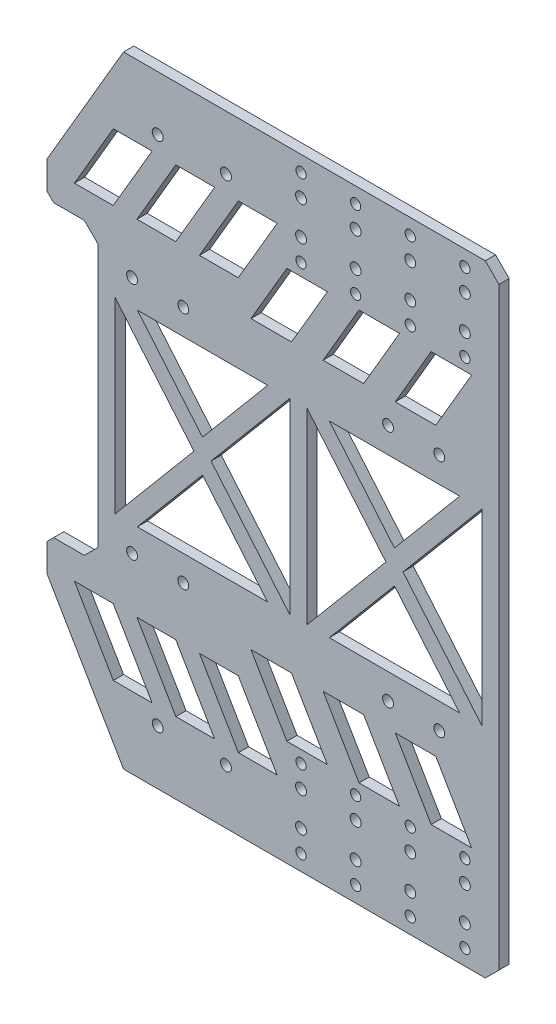
SolidWorks part; units mm, degrees
material "Thornel Mat VMA"
ref_plane "前视基准面" through (0, 0, 0) normal (0, 0, 1) x (1, 0, 0)
ref_plane "上视基准面" through (0, 0, 0) normal (0, 1, 0) x (1, 0, 0)
ref_plane "右视基准面" through (0, 0, 0) normal (1, 0, 0) x (0, 0, -1)
sketch "草图1" plane through (0, 0, 0) normal (0, 0, 1) x (1, 0, 0)
  line L1 (-99, 91) -> (99, 91)
  line L2 (-99, 91) -> (-99, -91)
  line L3 (-99, -91) -> (99, -91)
  line L4 (99, 91) -> (99, -91)
  line L5 (-99, 91) -> (99, -91) construction
  line L6 (-99, -91) -> (99, 91) construction
  point P0 (0, 0)
  dimension "D1" = 182
  dimension "D2" = 198
extrude "凸台-拉伸1" add sketch "草图1" along normal blind 3
sketch "草图3" plane through (0, 0, 0) normal (0, 0, -1) x (-1, 0, 0)
  line L0 (-39, -91) -> (-39, -80) construction
  line L1 (99, -91) -> (-99, -91) construction
  line L2 (-99, -91) -> (-99, 91) construction
  line L3 (-39, -80) -> (-39, -70) construction
  line L4 (87, -91) -> (87, -80) construction
  line L5 (99, 91) -> (99, -91) construction
  line L6 (87, -80) -> (87, -70) construction
  line L7 (0, 0) -> (-55, 0) construction
  line L8 (87, 80) -> (87, 70) construction
  line L9 (87, 91) -> (87, 80) construction
  line L10 (-39, 80) -> (-39, 70) construction
  line L11 (-39, 91) -> (-39, 80) construction
  circle A0 centre (-39, -80) radius 1.6
  circle A1 centre (-39, -70) radius 1.6
  circle A2 centre (-23, -80) radius 1.6
  circle A3 centre (-23, -70) radius 1.6
  circle A4 centre (-7, -80) radius 1.6
  circle A5 centre (-7, -70) radius 1.6
  circle A6 centre (9, -80) radius 1.6
  circle A7 centre (9, -70) radius 1.6
  circle A8 centre (87, -80) radius 1.6
  circle A9 centre (87, -70) radius 1.6
  circle A10 centre (71, -80) radius 1.6
  circle A11 centre (71, -70) radius 1.6
  circle A12 centre (55, -80) radius 1.6
  circle A13 centre (55, -70) radius 1.6
  circle A14 centre (39, -80) radius 1.6
  circle A15 centre (39, -70) radius 1.6
  circle A16 centre (39, 70) radius 1.6
  circle A17 centre (39, 80) radius 1.6
  circle A18 centre (55, 70) radius 1.6
  circle A19 centre (55, 80) radius 1.6
  circle A20 centre (71, 70) radius 1.6
  circle A21 centre (71, 80) radius 1.6
  circle A22 centre (87, 70) radius 1.6
  circle A23 centre (87, 80) radius 1.6
  circle A24 centre (9, 70) radius 1.6
  circle A25 centre (9, 80) radius 1.6
  circle A26 centre (-7, 70) radius 1.6
  circle A27 centre (-7, 80) radius 1.6
  circle A28 centre (-23, 70) radius 1.6
  circle A29 centre (-23, 80) radius 1.6
  circle A30 centre (-39, 70) radius 1.6
  circle A31 centre (-39, 80) radius 1.6
  dimension "D3" = 3.2
  dimension "D5" = 3.2
  dimension "D9" = 3.2
  dimension "D11" = 3.2
  dimension "D1" = 11
  dimension "D2" = 60
  dimension "D4" = 10
  dimension "D7" = 11
  dimension "D8" = 12
  dimension "D10" = 10
  dimension "D6" = 4
  dimension "D12" = 4
extrude "切除-拉伸2" cut sketch "草图3" against normal up to next (3 mm away)
sketch "草图4" plane through (0, 0, 0) normal (0, 0, -1) x (-1, 0, 0)
  line L0 (-99, -91) -> (-51, -91)
  line L1 (99, -91) -> (-99, -91) construction
  line L2 (-51, -91) -> (-51, 91)
  line L3 (-99, 91) -> (99, 91) construction
  line L4 (-51, 91) -> (-99, 91)
  line L5 (-99, 91) -> (-99, -91)
  dimension "D1" = 48
extrude "切除-拉伸3" cut sketch "草图4" against normal up to next
sketch "草图5" plane through (0, 0, 3) normal (0, 0, 1) x (1, 0, 0)
  line L0 (-99, 0) -> (-139, 0) construction
  line L3 (-99, 91) -> (-99, -91) construction
  line L4 (-99, -91) -> (51, -91) construction
  line L5 (-98.9551, 56) -> (-139.0449, 56)
  line L6 (-98.9551, 56) -> (-98.9551, -56)
  line L7 (-98.9551, -56) -> (-139.0449, -56)
  line L8 (-139.0449, 56) -> (-139.0449, -56)
  line L9 (-98.9551, 56) -> (-139.0449, -56) construction
  line L10 (-98.9551, -56) -> (-139.0449, 56) construction
  point P5 (71, 0)
  point P6 (-119, 0)
  dimension "D1" = 40
  dimension "D2" = 35
extrude "凸台-拉伸2" add sketch "草图5" against normal up to surface (3 mm away) up to face at (40.6, 80, 0)
sketch "草图6" plane through (0, 0, 3) normal (0, 0, 1) x (1, 0, 0)
  line L0 (-99, -91) -> (51, -91) construction
  line L1 (51, -91) -> (51, 91) construction
  line L2 (51, 0) -> (-28.0996, 0) construction
  circle A0 centre (13, -37) radius 2.75
  circle A1 centre (13, 37) radius 2.75
  circle A2 centre (-57, 37) radius 2.75
  circle A3 centre (-57, -37) radius 2.75
  circle A4 centre (-127, 37) radius 2.75
  circle A5 centre (-127, -37) radius 2.75
  dimension "D3" = 5.5
  dimension "D1" = 54
  dimension "D2" = 38
  dimension "D4" = 3
extrude "切除-拉伸4" cut sketch "草图6" against normal up to next
sketch "草图7" plane through (0, 0, 3) normal (0, 0, 1) x (1, 0, 0)
  line L0 (51, 0) -> (-44.0224, 0) construction
  line L1 (51, -91) -> (51, 91) construction
  line L3 (-44.0224, 0) -> (-44.0224, 48.7453) construction
  line L4 (-29.0112, -15) -> (-19.0112, -25)
  line L5 (-19.0112, -25) -> (25.9888, -25)
  line L6 (-29.0112, -15) -> (-29.0112, 15)
  line L7 (-19.0112, 25) -> (25.9888, 25)
  line L8 (35.9888, -15) -> (35.9888, 15)
  line L9 (-29.0112, -25) -> (35.9888, 25) construction
  line L10 (-29.0112, 25) -> (35.9888, -25) construction
  line L11 (-29.0112, 15) -> (-19.0112, 25)
  line L12 (25.9888, -25) -> (35.9888, -15)
  line L13 (35.9888, 15) -> (25.9888, 25)
  line L14 (-114.0337, -25) -> (-124.0337, -15)
  line L15 (-124.0337, -15) -> (-124.0337, 15)
  line L16 (-124.0337, 15) -> (-114.0337, 25)
  line L17 (-69.0337, 25) -> (-114.0337, 25)
  line L18 (-59.0337, 15) -> (-69.0337, 25)
  line L19 (-59.0337, -15) -> (-59.0337, 15)
  line L20 (-59.0337, -15) -> (-69.0337, -25)
  line L21 (-69.0337, -25) -> (-114.0337, -25)
  point P1 (3.4888, 0)
  dimension "D1" = 50
  dimension "D2" = 65
extrude "切除-拉伸5" cut sketch "草图7" against normal up to next
sketch "草图8" plane through (0, 0, 3) normal (0, 0, 1) x (1, 0, 0)
  line L0 (-99, -56) -> (-139.0449, -56)
  line L1 (-139.0449, -56) -> (-99, -91)
  line L2 (-99, -91) -> (-99, -56)
  line L3 (-139.0449, 56) -> (-99, 91)
  line L4 (-99, 91) -> (-99, 56)
  line L5 (-99, 56) -> (-139.0449, 56)
extrude "凸台-拉伸3" add sketch "草图8" against normal up to surface (3 mm away) up to face at (-91.5337, 0, 0)
sketch "草图10" plane through (0, 0, 3) normal (0, 0, 1) x (1, 0, 0)
  line L0 (-139.0449, 0) -> (51, 0) construction
  line L1 (-139.0449, 56) -> (-139.0449, -56) construction
  line L2 (51, -91) -> (51, 91) construction
  line L3 (-127, -42) -> (-127, -55.7313)
  line L4 (-127, -55.7313) -> (-115.2512, -66)
  line L5 (-115.2512, -66) -> (41, -66)
  line L6 (41, -66) -> (41, 66)
  line L7 (-127, -32) -> (-127, 32)
  line L8 (-99, -91) -> (51, -91) construction
  line L10 (-115.2512, 66) -> (41, 66)
  line L11 (-127, 55.7313) -> (-115.2512, 66)
  line L12 (-127, 42) -> (-127, 55.7313)
  circle A0 centre (-57, 37) radius 5
  circle A1 centre (-127, 37) radius 5
  circle A2 centre (13, 37) radius 5
  arc A3 (-127, -42) -> (-127, -32) centre (-127, -37) ccw
  circle A4 centre (-57, -37) radius 5
  circle A5 centre (13, -37) radius 5
  point P33 (41, 0)
  point P37 (-127, 0)
  dimension "D1" = 10
  dimension "D2" = 10
  dimension "D3" = 10
  dimension "D4" = 10
  dimension "D5" = 10
  dimension "D6" = 10
  dimension "D7" = 10
  dimension "D8" = 25
extrude "切除-拉伸6" cut sketch "草图10" against normal blind 10 contours L7 L0 L6 L10 L11 L12 A1 A0 A2 | L0 L7 A3 L3 L4 L5 L6 A5 A4 region at (-42.5617, 32.7628, 3) region at (-42.5617, -32.7628, 3)
sketch "草图11" plane through (0, 0, 3) normal (0, 0, 1) x (1, 0, 0)
  line L0 (-124.25, -37) -> (-59.75, -37)
  line L1 (-57, -39.75) -> (-57, -67.3473)
  line L2 (-54.25, -37) -> (10.25, -37)
  line L3 (13, -39.75) -> (13, -67.3473)
  line L4 (-124.25, 37) -> (-59.75, 37)
  line L5 (15.75, -37) -> (43.7296, -37)
  line L6 (-54.25, 37) -> (10.25, 37)
  line L7 (15.75, 37) -> (41.6506, 37)
  circle A0 centre (-127, -37) radius 2.75 construction
  circle A1 centre (-57, -37) radius 2.75 construction
  circle A2 centre (13, -37) radius 2.75 construction
  circle A3 centre (-127, 37) radius 2.75 construction
  circle A4 centre (-57, 37) radius 2.75 construction
  circle A5 centre (13, 37) radius 2.75 construction
extrude "拉伸-薄壁1" add sketch "草图11" against normal up to surface (3 mm away) thin up to face at (37.4, -80, 0) thin type mid plane wall 5
sketch "草图12" plane through (0, 0, 3) normal (0, 0, 1) x (1, 0, 0)
  line L0 (-57, 39.75) -> (-57, 67.3397)
  line L1 (13, 39.75) -> (13, 68.5019)
  line L2 (13, -34.25) -> (13, 34.25)
  line L3 (-57, -34.25) -> (-57, 34.25)
  circle A0 centre (-57, 37) radius 2.75 construction
  circle A1 centre (13, 37) radius 2.75 construction
  circle A2 centre (13, -37) radius 2.75 construction
  circle A3 centre (-57, -37) radius 2.75 construction
extrude "拉伸-薄壁2" add sketch "草图12" against normal up to surface (3 mm away) thin up to face at (-42.3336, 0, 0) thin type mid plane wall 5
sketch "草图13" plane through (0, 0, 3) normal (0, 0, 1) x (1, 0, 0)
  line L0 (-57, -37) -> (13, 37)
  line L2 (-57, 37) -> (-56.3876, 37.2464)
extrude "拉伸-薄壁3" add sketch "草图13" against normal up to surface (3 mm away) thin up to face at (-22, 0, 0) thin type mid plane wall 5
sketch "草图14" plane through (0, 0, 0) normal (0, 0, -1) x (-1, 0, 0)
  line L0 (57, 37) -> (-13, -37)
  line L1 (57.9332, 39.3193) -> (56.0668, 34.6807) construction
extrude "拉伸-薄壁4" add sketch "草图14" against normal up to surface (3 mm away) thin up to face at (-38.5889, 17.7076, 3) thin type mid plane wall 5
sketch "草图15" plane through (0, 0, 3) normal (0, 0, 1) x (1, 0, 0)
  line L0 (-55.1838, -38.718) -> (-58.8162, -35.282) construction
  line L2 (11.1838, -38.718) -> (14.8162, -35.282) construction
  line L3 (11.1838, 38.718) -> (14.8162, 35.282) construction
  circle A0 centre (-57, -37) radius 2.75
  circle A1 centre (-57, 37) radius 2.75
  circle A2 centre (13, 37) radius 2.75
  circle A3 centre (13, -37) radius 2.75
extrude "切除-拉伸7" cut sketch "草图15" against normal up to next
sketch "草图16" plane through (0, 0, 3) normal (0, 0, 1) x (1, 0, 0)
  line L0 (-57, -37) -> (-127, 37)
  line L1 (-57, 37) -> (-127, -37)
extrude "拉伸-薄壁5" add sketch "草图16" against normal up to surface (3 mm away) thin up to face at (-54.25, 37, 0) thin type mid plane wall 5
sketch "草图17" plane through (0, 0, 3) normal (0, 0, 1) x (1, 0, 0)
  line L0 (41, 34.5) -> (13, -37)
  line L1 (13, 37) -> (41, -34.5)
extrude "拉伸-薄壁6" add sketch "草图17" against normal up to surface (3 mm away) thin up to face at (-120.2229, 0, 0) thin type mid plane wall 5
sketch "草图18" plane through (0, 0, 0) normal (0, 0, -1) x (-1, 0, 0)
  line L0 (-10.6721, -36.0884) -> (-15.3279, -37.9116) construction
  line L1 (-15.3279, 37.9116) -> (-10.6721, 36.0884) construction
  line L2 (55.1838, 35.282) -> (58.8162, 38.718) construction
  line L3 (58.8162, -38.718) -> (55.1838, -35.282) construction
  line L4 (128.8162, -35.282) -> (125.1838, -38.718) construction
  line L5 (125.1838, 38.718) -> (128.8162, 35.282) construction
  circle A0 centre (-13, -37) radius 2.75
  circle A1 centre (-13, 37) radius 2.75
  circle A2 centre (57, 37) radius 2.75
  circle A3 centre (57, -37) radius 2.75
  circle A4 centre (127, -37) radius 2.75
  circle A5 centre (127, 37) radius 2.75
extrude "切除-拉伸8" cut sketch "草图18" against normal up to next
sketch "草图19" plane through (0, 0, 3) normal (0, 0, 1) x (1, 0, 0)
  line L0 (-57, 37) -> (10.5, 66)
  line L1 (13, 37) -> (-54.5, 66)
  line L2 (-127, 37) -> (-59.5, 66)
  line L3 (-57, 37) -> (-115.2512, 66)
  line L4 (13, 37) -> (41, 66)
  line L5 (15.5, 66) -> (41, 39.5)
extrude "拉伸-薄壁7" add sketch "草图19" against normal up to surface (3 mm away) thin up to face at (37.3915, 0, 0) thin type mid plane wall 5
sketch "草图20" plane through (0, 0, 0) normal (0, 0, -1) x (-1, 0, 0)
  line L0 (127.9869, 39.297) -> (126.0131, 34.703) construction
  circle A0 centre (-13, 37) radius 2.75
  circle A1 centre (57, 37) radius 2.75
  circle A2 centre (127, 37) radius 2.75
extrude "切除-拉伸9" cut sketch "草图20" against normal up to next
sketch "草图21" plane through (0, 0, 0) normal (0, 0, -1) x (-1, 0, 0)
  line L0 (-13, -37) -> (-41, -66)
  line L1 (-15.5, -66) -> (-41, -39.5)
  line L2 (-10.5, -66) -> (57, -37)
  line L3 (-13, -37) -> (54.5, -66)
  line L4 (57, -37) -> (115.2512, -66)
  line L5 (59.5, -66) -> (127, -37)
extrude "拉伸-薄壁8" add sketch "草图21" against normal up to surface (3 mm away) thin up to face at (-129.75, 37, 3) thin type mid plane wall 5
sketch "草图22" plane through (0, 0, 3) normal (0, 0, 1) x (1, 0, 0)
  line L0 (-126.0131, -34.703) -> (-127.9869, -39.297) construction
  circle A0 centre (-127, -37) radius 2.75
  circle A1 centre (-57, -37) radius 2.75
  circle A2 centre (13, -37) radius 2.75
extrude "切除-拉伸10" cut sketch "草图22" against normal up to next
sketch "草图23" plane through (0, 0, 3) normal (0, 0, 1) x (1, 0, 0)
  line L0 (-115.2512, 66) -> (-116.3654, 63.762)
  line L1 (-116.3654, 63.762) -> (-117.2869, 64.2208)
  line L2 (-127, 55.7313) -> (-115.2512, 66) construction
  line L3 (-117.2869, 64.2208) -> (-115.2512, 66)
  line L4 (-116.3654, -63.762) -> (-117.2869, -64.2208)
  line L5 (-127, -55.7313) -> (-115.2512, -66) construction
  line L6 (-117.2869, -64.2208) -> (-115.2512, -66)
  line L7 (-115.2512, -66) -> (-116.3654, -63.762)
extrude "凸台-拉伸4" add sketch "草图23" against normal up to surface (3 mm away) up to face at (-54.25, -37, 0)
sketch "草图24" plane through (0, 0, 0) normal (0, 0, -1) x (-1, 0, 0)
  line L0 (21.9465, 0) -> (-12.7555, 0)
extrude "拉伸-薄壁9" add sketch "草图24" against normal up to surface (3 mm away) thin up to face at (-118.1171, 51.302, 3) thin type mid plane wall 10
sketch "草图25" plane through (0, 0, 0) normal (0, 0, -1) x (-1, 0, 0)
  line L0 (20.7116, 5) -> (21.9465, 3.6945)
  line L1 (21.9465, 3.6945) -> (21.9465, 5)
  line L2 (21.9465, 5) -> (20.7116, 5)
  line L3 (20.7116, -5) -> (21.9465, -5)
  line L4 (21.9465, -5) -> (21.9465, -3.6945)
  line L5 (21.9465, -3.6945) -> (20.7116, -5)
extrude "切除-拉伸11" cut sketch "草图25" against normal up to next
sketch "草图26" plane through (0, 0, 0) normal (0, 0, -1) x (-1, 0, 0)
  line L0 (-13, -37) -> (-13, 37) construction
  line L1 (-13, 0) -> (7, 0) construction
  circle A0 centre (7, 0) radius 2.75
  dimension "D2" = 5.5
  dimension "D1" = 20
extrude "切除-拉伸12" cut sketch "草图26" against normal up to next
sketch "草图27" plane through (0, 0, 3) normal (0, 0, 1) x (1, 0, 0)
  line L0 (10.5, 5) -> (-2.3398, 17.1457)
  line L1 (-13.829, 5) -> (10.5, 30.7192) construction
  line L2 (-2.3398, 17.1457) -> (-13.829, 5)
  line L3 (-13.829, 5) -> (10.5, 5)
  line L4 (-13.829, -5) -> (10.5, -5)
  line L5 (10.5, -5) -> (-2.3398, -17.1457)
  line L6 (-13.829, -5) -> (10.5, -30.7192) construction
  line L7 (-2.3398, -17.1457) -> (-13.829, -5)
extrude "凸台-拉伸5" add sketch "草图27" against normal up to surface (3 mm away) up to face at (-9.75, 0, 0)
sketch "草图28" plane through (0, 0, 3) normal (0, 0, 1) x (1, 0, 0)
  line L1 (51, 91) -> (-199, 91)
  line L2 (51, 91) -> (51, -91)
  line L3 (51, -91) -> (-199, -91)
  line L4 (-199, 91) -> (-199, -91)
  circle A1 centre (-87, -70) radius 1.6
  circle A2 centre (-87, -70) radius 1.6
  circle A3 centre (-87, -80) radius 1.6
  circle A4 centre (-87, -80) radius 1.6
  circle A5 centre (-71, -70) radius 1.6
  circle A6 centre (-71, -70) radius 1.6
  circle A7 centre (-71, -80) radius 1.6
  circle A8 centre (-71, -80) radius 1.6
  circle A9 centre (-55, -70) radius 1.6
  circle A10 centre (-55, -70) radius 1.6
  circle A11 centre (-55, -80) radius 1.6
  circle A12 centre (-55, -80) radius 1.6
  circle A13 centre (-39, -70) radius 1.6
  circle A14 centre (-39, -70) radius 1.6
  circle A15 centre (-39, -80) radius 1.6
  circle A16 centre (-39, -80) radius 1.6
  circle A17 centre (-87, 80) radius 1.6
  circle A18 centre (-87, 80) radius 1.6
  circle A19 centre (-87, 70) radius 1.6
  circle A20 centre (-87, 70) radius 1.6
  circle A21 centre (-71, 80) radius 1.6
  circle A22 centre (-71, 80) radius 1.6
  circle A23 centre (-71, 70) radius 1.6
  circle A24 centre (-71, 70) radius 1.6
  circle A25 centre (-55, 80) radius 1.6
  circle A26 centre (-55, 80) radius 1.6
  circle A27 centre (-55, 70) radius 1.6
  circle A28 centre (-55, 70) radius 1.6
  circle A29 centre (-39, 80) radius 1.6
  circle A30 centre (-39, 80) radius 1.6
  circle A31 centre (-39, 70) radius 1.6
  circle A32 centre (-39, 70) radius 1.6
  dimension "D1" = 250
  dimension "D2" = 0
  dimension "D3" = 0
  dimension "D4" = 0
  dimension "D5" = 0
  dimension "D6" = 0
  dimension "D7" = 0
  dimension "D8" = 0
  dimension "D9" = 0
  dimension "D10" = 0
  dimension "D11" = 0
  dimension "D12" = 0
  dimension "D13" = 0
  dimension "D14" = 0
  dimension "D15" = 0
  dimension "D16" = 0
  dimension "D17" = 0
extrude "凸台-拉伸6" add sketch "草图28" against normal up to surface (3 mm away) up to face at (6.2201, -17.6216, 0)
sketch "草图29" plane through (0, 0, 3) normal (0, 0, 1) x (1, 0, 0)
  line L0 (-199, 0) -> (51, 0) construction
  line L1 (-199, 91) -> (-199, -91) construction
  line L2 (51, -91) -> (51, 91) construction
  line L3 (-99, 101.3462) -> (-99, -102.1359) construction
  circle A0 centre (-129, 75) radius 1.6
  circle A1 centre (-109, 75) radius 1.6
  circle A2 centre (-87, 80) radius 1.6 construction
  circle A3 centre (-109, -75) radius 1.6
  circle A4 centre (-129, -75) radius 1.6
  dimension "D1" = 3.2
  dimension "D2" = 12
  dimension "D3" = 20
  dimension "D4" = 10
  dimension "D5" = 150
extrude "切除-拉伸13" cut sketch "草图29" against normal through all
sketch "草图30" plane through (0, 0, 3) normal (0, 0, 1) x (1, 0, 0)
  line L0 (-237.129, 0) -> (65.8362, 0) construction
  line L1 (-129, 75) -> (-129, -79.7546) construction
  line L2 (-91.5, 48.8314) -> (-91.5, -56.1435) construction
  line L3 (-54, 75) -> (-54, -79.7546) construction
  circle A0 centre (-136.5, 35) radius 1.6
  circle A1 centre (-121.5, 35) radius 1.6
  circle A2 centre (-121.5, -35) radius 1.6
  circle A3 centre (-136.5, -35) radius 1.6
  circle A4 centre (-46.5, -35) radius 1.6
  circle A5 centre (-61.5, -35) radius 1.6
  circle A6 centre (-61.5, 35) radius 1.6
  circle A7 centre (-46.5, 35) radius 1.6
  dimension "D1" = 3.2
  dimension "D2" = 15
  dimension "D3" = 70
  dimension "D4" = 75
extrude "切除-拉伸14" cut sketch "草图30" against normal through all
sketch "草图31" plane through (0, 0, 3) normal (0, 0, 1) x (1, 0, 0)
  line L0 (-230.0358, 0) -> (62.3162, 0) construction
  line L1 (-146.5, -42.5) -> (-146.5, 42.5)
  line L2 (-146.5, 42.5) -> (-161.5, 42.5)
  line L3 (-161.5, 42.5) -> (-161.5, 52.5)
  line L4 (-161.5, 52.5) -> (-139, 91)
  line L5 (51, 91) -> (-199, 91) construction
  line L6 (-139, 91) -> (-29, 91)
  line L7 (-29, 91) -> (-29, -91)
  line L8 (-139, -91) -> (-29, -91)
  line L9 (-161.5, -52.5) -> (-139, -91)
  line L10 (-161.5, -42.5) -> (-161.5, -52.5)
  line L11 (-146.5, -42.5) -> (-161.5, -42.5)
  line L12 (-161.5, 47.5) -> (-62.7875, 47.5) construction
  circle A4 centre (-136.5, 35) radius 1.6 construction
  circle A5 centre (-129, 75) radius 1.6 construction
  circle A6 centre (-39, 70) radius 1.6 construction
  point P13 (-29, 0)
  point P17 (-146.5, 0)
  dimension "D1" = 12.5
  dimension "D6" = 10
  dimension "D2" = 10
  dimension "D3" = 10
  dimension "D4" = 25
  dimension "D5" = 10
extrude "切除-拉伸15" cut sketch "草图31" against normal through all flip side to cut
sketch "草图32" plane through (0, 0, 3) normal (0, 0, 1) x (1, 0, 0)
  line L0 (-87.75, 50.5) -> (-87.75, -64.2739) construction
  line L1 (-134.9671, 27.5) -> (-96.7829, 27.5)
  line L2 (-141.5, 27.5) -> (-141.5, -27.5)
  line L3 (-134.9671, -27.5) -> (-96.7829, -27.5)
  line L4 (-90.25, 27.5) -> (-90.25, -27.5)
  line L5 (-85.25, 27.5) -> (-85.25, -27.5)
  line L6 (-40.5329, -27.5) -> (-78.7171, -27.5)
  line L7 (-34, 27.5) -> (-34, -27.5)
  line L8 (-40.5329, 27.5) -> (-78.7171, 27.5)
  line L9 (-146.5, 0) -> (-29, 0) construction
  line L10 (-146.5, 42.5) -> (-146.5, -42.5) construction
  line L11 (-29, -91) -> (-29, 91) construction
  line L14 (-141.5, 27.5) -> (-118.375, 0)
  line L15 (-118.375, 0) -> (-141.5, -27.5)
  line L16 (-115.875, 27.5) -> (-115.875, -27.5) construction
  line L17 (-113.375, 0) -> (-90.25, -27.5)
  line L18 (-90.25, 27.5) -> (-113.375, 0)
  line L19 (-134.9671, -27.5) -> (-115.875, -4.7958)
  line L20 (-115.875, -4.7958) -> (-96.7829, -27.5)
  line L21 (-115.875, 4.7958) -> (-96.7829, 27.5)
  line L22 (-134.9671, 27.5) -> (-115.875, 4.7958)
  line L23 (-59.625, 4.7958) -> (-78.7171, 27.5)
  line L24 (-85.25, 27.5) -> (-62.125, 0)
  line L25 (-62.125, 0) -> (-85.25, -27.5)
  line L26 (-59.625, -4.7958) -> (-78.7171, -27.5)
  line L27 (-40.5329, -27.5) -> (-59.625, -4.7958)
  line L28 (-57.125, 0) -> (-34, -27.5)
  line L29 (-34, 27.5) -> (-57.125, 0)
  line L30 (-40.5329, 27.5) -> (-59.625, 4.7958)
  line L31 (-153.4028, 50.5) -> (-142.0336, 50.5)
  line L32 (-153.4028, 50.5) -> (-142.0067, 70)
  line L33 (-142.0336, 50.5) -> (-130.6375, 70)
  line L34 (-142.0067, 70) -> (-130.6375, 70)
  line L35 (-135.0841, 50.5) -> (-123.7148, 50.5)
  line L36 (-135.0841, 50.5) -> (-123.688, 70)
  line L37 (-123.7148, 50.5) -> (-112.3187, 70)
  line L38 (-123.688, 70) -> (-112.3187, 70)
  line L39 (-116.7654, 50.5) -> (-105.3961, 50.5)
  line L40 (-116.7654, 50.5) -> (-105.3692, 70)
  line L41 (-105.3961, 50.5) -> (-94, 70)
  line L42 (-105.3692, 70) -> (-94, 70)
  line L43 (-139, 91) -> (-161.5, 52.5) construction
  line L44 (-161.5, 42.5) -> (-146.5, 42.5) construction
  line L45 (-101.6768, 42) -> (-89.8017, 42)
  line L46 (-101.6768, 42) -> (-91.1573, 60)
  line L47 (-89.8017, 42) -> (-79.2822, 60)
  line L48 (-91.1573, 60) -> (-79.2822, 60)
  line L49 (-80.5357, 42) -> (-70.0162, 60)
  line L50 (-68.6606, 42) -> (-58.1411, 60)
  line L51 (-70.0162, 60) -> (-58.1411, 60)
  line L52 (-80.5357, 42) -> (-68.6606, 42)
  line L53 (-59.3946, 42) -> (-48.8751, 60)
  line L54 (-47.5195, 42) -> (-37, 60)
  line L55 (-48.8751, 60) -> (-37, 60)
  line L56 (-59.3946, 42) -> (-47.5195, 42)
  line L57 (-59.3946, -42) -> (-47.5195, -42)
  line L58 (-48.8751, -60) -> (-37, -60)
  line L59 (-47.5195, -42) -> (-37, -60)
  line L60 (-59.3946, -42) -> (-48.8751, -60)
  line L61 (-80.5357, -42) -> (-68.6606, -42)
  line L62 (-70.0162, -60) -> (-58.1411, -60)
  line L63 (-68.6606, -42) -> (-58.1411, -60)
  line L64 (-80.5357, -42) -> (-70.0162, -60)
  line L65 (-91.1573, -60) -> (-79.2822, -60)
  line L66 (-89.8017, -42) -> (-79.2822, -60)
  line L67 (-101.6768, -42) -> (-91.1573, -60)
  line L68 (-101.6768, -42) -> (-89.8017, -42)
  line L69 (-105.3692, -70) -> (-94, -70)
  line L70 (-105.3961, -50.5) -> (-94, -70)
  line L71 (-116.7654, -50.5) -> (-105.3692, -70)
  line L72 (-116.7654, -50.5) -> (-105.3961, -50.5)
  line L73 (-123.688, -70) -> (-112.3187, -70)
  line L74 (-123.7148, -50.5) -> (-112.3187, -70)
  line L75 (-135.0841, -50.5) -> (-123.688, -70)
  line L76 (-135.0841, -50.5) -> (-123.7148, -50.5)
  line L77 (-142.0067, -70) -> (-130.6375, -70)
  line L78 (-142.0336, -50.5) -> (-130.6375, -70)
  line L79 (-153.4028, -50.5) -> (-142.0067, -70)
  line L80 (-153.4028, -50.5) -> (-142.0336, -50.5)
  circle A0 centre (-121.5, 35) radius 1.6 construction
  circle A1 centre (-129, 75) radius 1.6 construction
  circle A2 centre (-87, 70) radius 1.6 construction
  dimension "D4" = 7.5
  dimension "D11" = 5
  dimension "D1" = 5
  dimension "D2" = 5
  dimension "D3" = 5
  dimension "D5" = 5
  dimension "D6" = 5
  dimension "D8" = 8
  dimension "D9" = 6
  dimension "D10" = 8
  dimension "D12" = 7
  dimension "D13" = 10
  dimension "D14" = 7
  dimension "D15" = 7.5
  dimension "D17" = 8
  dimension "D18" = 8
  dimension "D7" = 3
  dimension "D16" = 3
extrude "切除-拉伸16" cut sketch "草图32" against normal through all
chamfer "倒角1" distance 2 angle 45 2 edges at (-161.5, -42.5, 1.5) (-161.5, 42.5, 1.5)
chamfer "倒角2" distance 4 angle 45 4 edges at (-29, 91, 1.5) (-29, -91, 1.5) (-146.5, -42.5, 1.5) (-146.5, 42.5, 1.5)
sketch "草图34" plane through (0, 0, 0) normal (0, 0, -1) x (-1, 0, 0)
  line L0 (0, 0) -> (194.3682, 0) construction
  circle A0 centre (71, -86.4) radius 1.5 construction
  circle A1 centre (55, -86.4) radius 1.5 construction
  circle A2 centre (39, -86.4) radius 1.5 construction
  circle A3 centre (87, -86.4) radius 1.5 construction
  circle A4 centre (87, -63.6) radius 1.5 construction
  circle A5 centre (71, -63.6) radius 1.5 construction
  circle A6 centre (55, -63.6) radius 1.5 construction
  circle A7 centre (39, -63.6) radius 1.5 construction
  circle A8 centre (71, -86.4) radius 1.5
  circle A9 centre (55, -86.4) radius 1.5
  circle A10 centre (39, -86.4) radius 1.5
  circle A11 centre (87, -86.4) radius 1.5
  circle A12 centre (87, -63.6) radius 1.5
  circle A13 centre (71, -63.6) radius 1.5
  circle A14 centre (55, -63.6) radius 1.5
  circle A15 centre (39, -63.6) radius 1.5
  circle A16 centre (39, 63.6) radius 1.5
  circle A17 centre (55, 63.6) radius 1.5
  circle A18 centre (71, 63.6) radius 1.5
  circle A19 centre (87, 63.6) radius 1.5
  circle A20 centre (87, 86.4) radius 1.5
  circle A21 centre (39, 86.4) radius 1.5
  circle A22 centre (55, 86.4) radius 1.5
  circle A23 centre (71, 86.4) radius 1.5
extrude "切除-拉伸17" cut sketch "草图34" against normal through all
